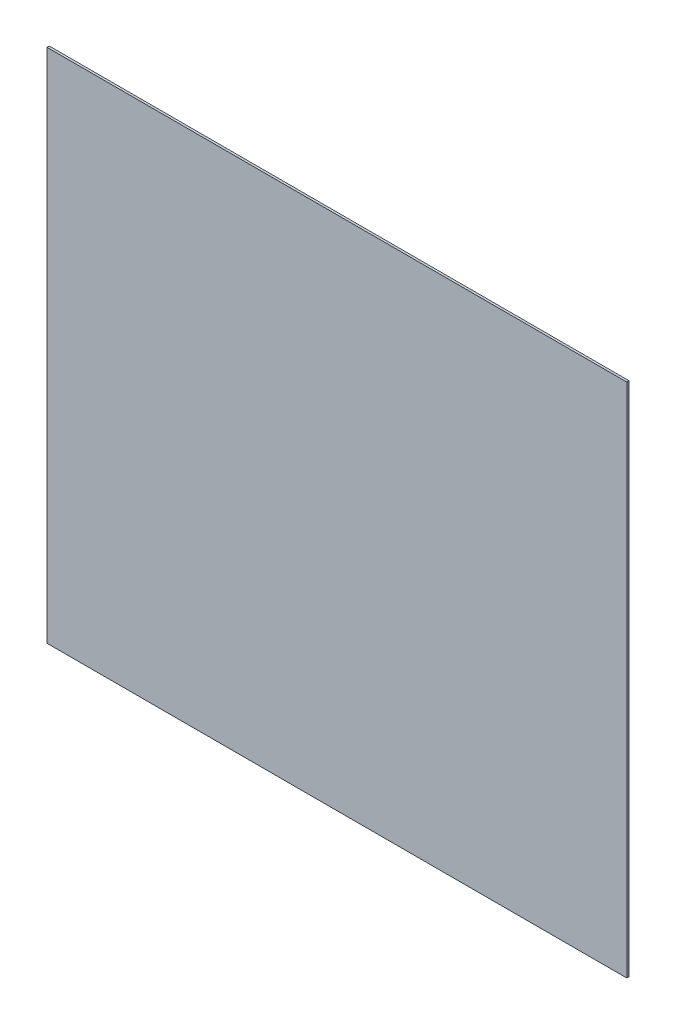
SolidWorks part; units mm, degrees
material "Mahogany"
ref_plane "Front Plane" through (0, 0, 0) normal (0, 0, 1) x (1, 0, 0)
ref_plane "Top Plane" through (0, 0, 0) normal (0, 1, 0) x (1, 0, 0)
ref_plane "Right Plane" through (0, 0, 0) normal (1, 0, 0) x (0, 0, -1)
sketch "Sketch1" plane through (0, 0, 0) normal (0, 0, 1) x (1, 0, 0)
  line L1 (-410, -365) -> (410, -365)
  line L2 (-410, -365) -> (-410, 365)
  line L3 (-410, 365) -> (410, 365)
  line L4 (410, -365) -> (410, 365)
  line L5 (-410, -365) -> (410, 365) construction
  line L6 (-410, 365) -> (410, -365) construction
  point P0 (0, 0)
  dimension "D1" = 820
  dimension "D2" = 730
extrude "Boss-Extrude1" add sketch "Sketch1" along normal blind 3.175
equation "\"W\"= 1700"
equation "\"L\"= 760"
equation "\"H\"= 810"
equation "\"ARM_BOLT_SPACING\"= 166"
equation "\"ARM_TO_WALL\"= 300"
equation "\"D1@Sketch1\"=(\"W\"/2)-30"
equation "\"D2@Sketch1\"=\"H\"-80"
